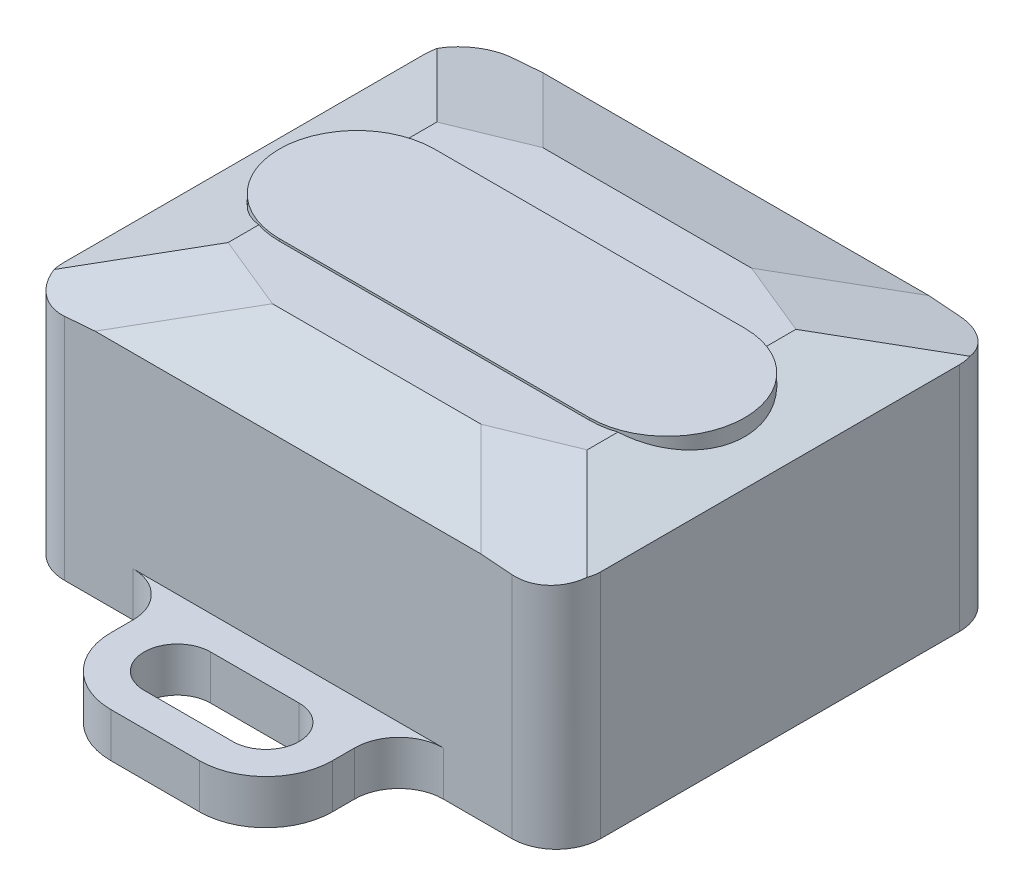
SolidWorks part; units mm, degrees
ref_plane "前视基准面" through (0, 0, 0) normal (0, 0, 1) x (1, 0, 0)
ref_plane "上视基准面" through (0, 0, 0) normal (0, 1, 0) x (1, 0, 0)
ref_plane "右视基准面" through (0, 0, 0) normal (1, 0, 0) x (0, 0, -1)
sketch "草图1" plane through (0, 0, 0) normal (0, 1, 0) x (1, 0, 0)
  line L1 (0, 0) -> (24.2, 0)
  line L2 (0, 0) -> (0, 20.2)
  line L3 (0, 20.2) -> (24.2, 20.2)
  line L4 (24.2, 0) -> (24.2, 20.2)
  dimension "D1" = 24.2
  dimension "D2" = 20.2
extrude "凸台-拉伸1" add sketch "草图1" along normal blind 11.5
sketch "草图2" plane through (0, 0, 0) normal (0, -1, 0) x (1, 0, 0)
  line L0 (0, -10.1) -> (24.2, -10.1) construction
  line L1 (0, -20.2) -> (0, 0) construction
  line L2 (24.2, 0) -> (24.2, -20.2) construction
  line L3 (12.1, -23.2) -> (12.1, 3) construction
  line L4 (14.1, 3) -> (10.1, 3) construction
  line L5 (14.1, 1.5) -> (10.1, 1.5)
  line L6 (14.1, 4.5) -> (10.1, 4.5)
  line L7 (14.1, 3) -> (10.1, 3) construction
  line L8 (17.1, 0) -> (7.1, 0)
  line L9 (14.1, 6) -> (10.1, 6)
  line L10 (17.1, 3) -> (17.1, 0)
  line L11 (0, 0) -> (24.2, 0) construction
  line L12 (7.1, 3) -> (7.1, 0)
  line L13 (14.1, -23.2) -> (10.1, -23.2) construction
  line L14 (7.1, -23.2) -> (7.1, -20.2)
  line L15 (17.1, -23.2) -> (17.1, -20.2)
  line L16 (14.1, -26.2) -> (10.1, -26.2)
  line L17 (17.1, -20.2) -> (7.1, -20.2)
  line L18 (14.1, -23.2) -> (10.1, -23.2) construction
  line L19 (14.1, -21.7) -> (10.1, -21.7)
  line L20 (14.1, -24.7) -> (10.1, -24.7)
  arc A0 (14.1, 1.5) -> (14.1, 4.5) centre (14.1, 3) ccw
  arc A1 (10.1, 4.5) -> (10.1, 1.5) centre (10.1, 3) ccw
  arc A2 (17.1, 3) -> (14.1, 6) centre (14.1, 3) ccw
  arc A3 (10.1, 6) -> (7.1, 3) centre (10.1, 3) ccw
  arc A4 (10.1, -26.2) -> (7.1, -23.2) centre (10.1, -23.2) cw
  arc A5 (17.1, -23.2) -> (14.1, -26.2) centre (14.1, -23.2) cw
  arc A6 (14.1, -21.7) -> (14.1, -24.7) centre (14.1, -23.2) cw
  arc A7 (10.1, -24.7) -> (10.1, -21.7) centre (10.1, -23.2) cw
  point P10 (12.1, 3)
  point P15 (12.1, 3)
  point P18 (7.1, 0)
  point P19 (17.1, -0.1246)
  point P28 (7.2458, 0)
  point P29 (0, 0)
  point P33 (12.1, -10.1)
  point P39 (12.1, -23.2)
  point P40 (12.1, -23.2)
  dimension "D1" = 13.1
  dimension "D2" = 3
  dimension "D3" = 4
  dimension "D4" = 16.1
extrude "凸台-拉伸2" add sketch "草图2" against normal blind 2
fillet "圆角1" radius 2 4 edges at (17.1, 1, -20.2) (7.1, 1, -20.2) (7.1, 1, 0) (17.1, 1, 0)
sketch "草图3" plane through (0, 11.5, 0) normal (0, 1, 0) x (1, 0, 0)
  line L0 (0, 10.1) -> (24.2, 10.1) construction
  line L1 (0, 20.2) -> (0, 0) construction
  line L2 (24.2, 0) -> (24.2, 20.2) construction
  line L3 (5.1, 10.1) -> (19.1, 10.1) construction
  line L4 (5.1, 13.6) -> (19.1, 13.6)
  line L5 (5.1, 6.6) -> (19.1, 6.6)
  arc A0 (5.1, 13.6) -> (5.1, 6.6) centre (5.1, 10.1) ccw
  arc A1 (19.1, 6.6) -> (19.1, 13.6) centre (19.1, 10.1) ccw
  point P8 (12.1, 10.1)
  point P13 (0, 0)
  dimension "D1" = 3.5
  dimension "D2" = 14
extrude "凸台-拉伸3" add sketch "草图3" along normal blind 0.1
chamfer "倒角1" distance 4 angle 15 4 edges at (12.1, 11.5, -20.2) (24.2, 11.5, -10.1) (0, 11.5, -10.1) (12.1, 11.5, 0) first distance on face at (12.1, 11.5, -10.1)
chamfer "倒角3" distance 1 angle 15 4 edges at (22.2, 10.9641, -18.2) (2, 10.9641, -18.2) (2, 10.9641, -2) (22.2, 10.9641, -2) first distance on face at (21.9333, 11.0356, -10.1) first distance on face at (2.2667, 11.0356, -10.1)
fillet "圆角2" radius 2 4 edges at (0, 5.082, 0) (0, 5.082, -20.2) (24.2, 5.082, -20.2) (24.2, 5.082, 0)
